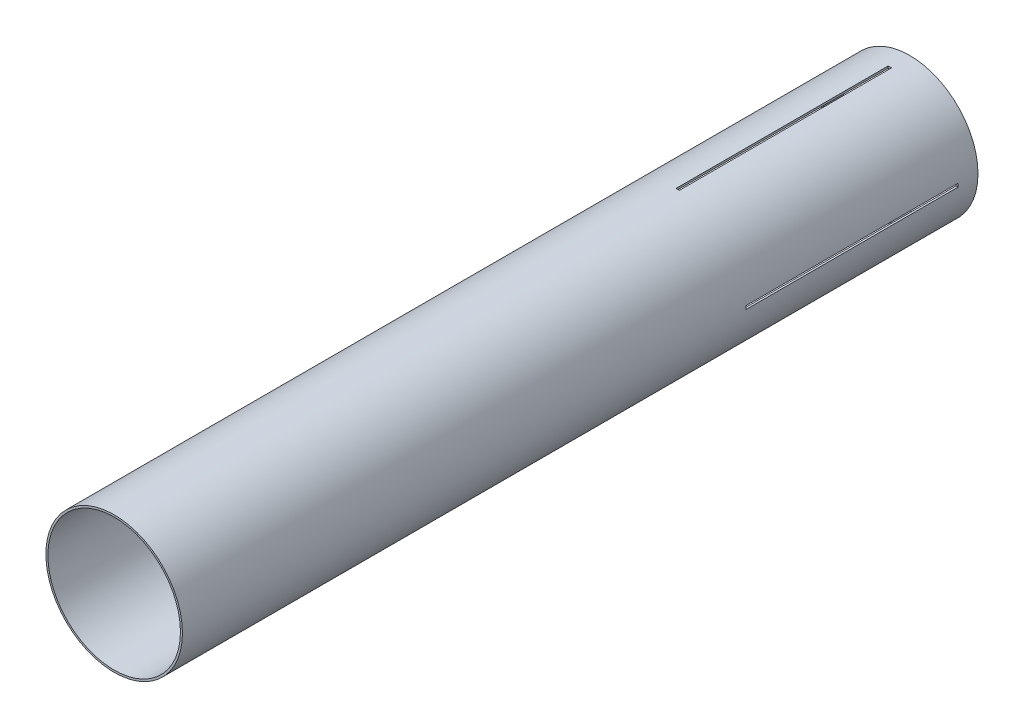
SolidWorks part; units mm, degrees
ref_plane "Front Plane" through (0, 0, 0) normal (0, 0, 1) x (1, 0, 0)
ref_plane "Top Plane" through (0, 0, 0) normal (0, 1, 0) x (1, 0, 0)
ref_plane "Right Plane" through (0, 0, 0) normal (1, 0, 0) x (0, 0, -1)
sketch "Sketch1" plane through (0, 0, 0) normal (0, 0, 1) x (1, 0, 0)
  circle A0 centre (0, 0) radius 65.405
  circle A1 centre (0, 0) radius 63.5
  dimension "D1" = 127
  dimension "D2" = 130.81
extrude "Boss-Extrude1" add sketch "Sketch1" along normal mid plane 762
sketch "Sketch3" plane through (0, 0, 0) normal (0, 1, 0) x (1, 0, 0)
  line L0 (65.405, 381) -> (-65.405, 381) construction
  line L1 (1.5875, 158.75) -> (-1.5875, 158.75)
  line L2 (1.5875, 158.75) -> (1.5875, 361.95)
  line L3 (1.5875, 361.95) -> (-1.5875, 361.95)
  line L4 (-1.5875, 158.75) -> (-1.5875, 361.95)
  line L5 (1.5875, 158.75) -> (-1.5875, 361.95) construction
  line L6 (1.5875, 361.95) -> (-1.5875, 158.75) construction
  line L7 (65.405, 381) -> (-65.405, 381) construction
  point P0 (0, 260.35)
  dimension "D2" = 203.2
  dimension "D3" = 19.05
extrude "Cut-Extrude1" cut sketch "Sketch3" along normal through all
pattern_circular "CirPattern1" count 4 over 360 about axis through (0, 0, 381) along (0, 0, -1) of "Cut-Extrude1" reverse direction yes
equation "\"AIRFRAME_OD\"= 5.15in"
equation "\"AIRFRAME_ID\"= 5.00in"
equation "\"FLAT_T\"= 0.125in"
equation "\"NOSE_EXP_L\"= 27in"
equation "\"NOSE_SHOULDER_L\"= 5in"
equation "\"MAIN_L\"= 30in"
equation "\"RECO_COUP_L\"= 10in"
equation "\"RECO_SWITCH_L\"= 2in"
equation "\"DROGUE_L\"= 20in"
equation "\"ATS_FORE_COUP_L\"= 5.5in"
equation "\"ATS_AFT_COUP_L\"= 4.5in"
equation "\"LOWER_L\"= 30in"
equation "\"FIN_N\"= 4"
equation "\"CR_AFT_X\"= 0.5in"
equation "\"CR_FORE_X\"= 9.25in"
equation "\"D1@Sketch1\"=\"AIRFRAME_ID\""
equation "\"D2@Sketch1\"=\"AIRFRAME_OD\""
equation "\"D1@Boss-Extrude1\"=\"LOWER_L\""
equation "\"FIN_ROOT\"= 8in"
equation "\"FIN_X\"= 0.75in"
equation "\"MOTOR_OD\"= 3.091in"
equation "\"MOTOR_ID\"= 3.00in"
equation "\"D1@Sketch3\"=\"FLAT_T\""
equation "\"D2@Sketch3\"=\"FIN_ROOT\""
equation "\"D3@Sketch3\"=\"FIN_X\""
equation "\"D1@CirPattern1\"=\"FIN_N\""
equation "\"COUPLER_OD\"= 4.998in"
equation "\"COUPLER_ID\"= 4.88in"
equation "\"RECO_ROD_X\"= 3.5in"
equation "\"ATS_ROD_X\"= 3in"
equation "\"MOTOR_L\"= 14in"
equation "\"MOTOR_LOWER_X\"= 2in"
